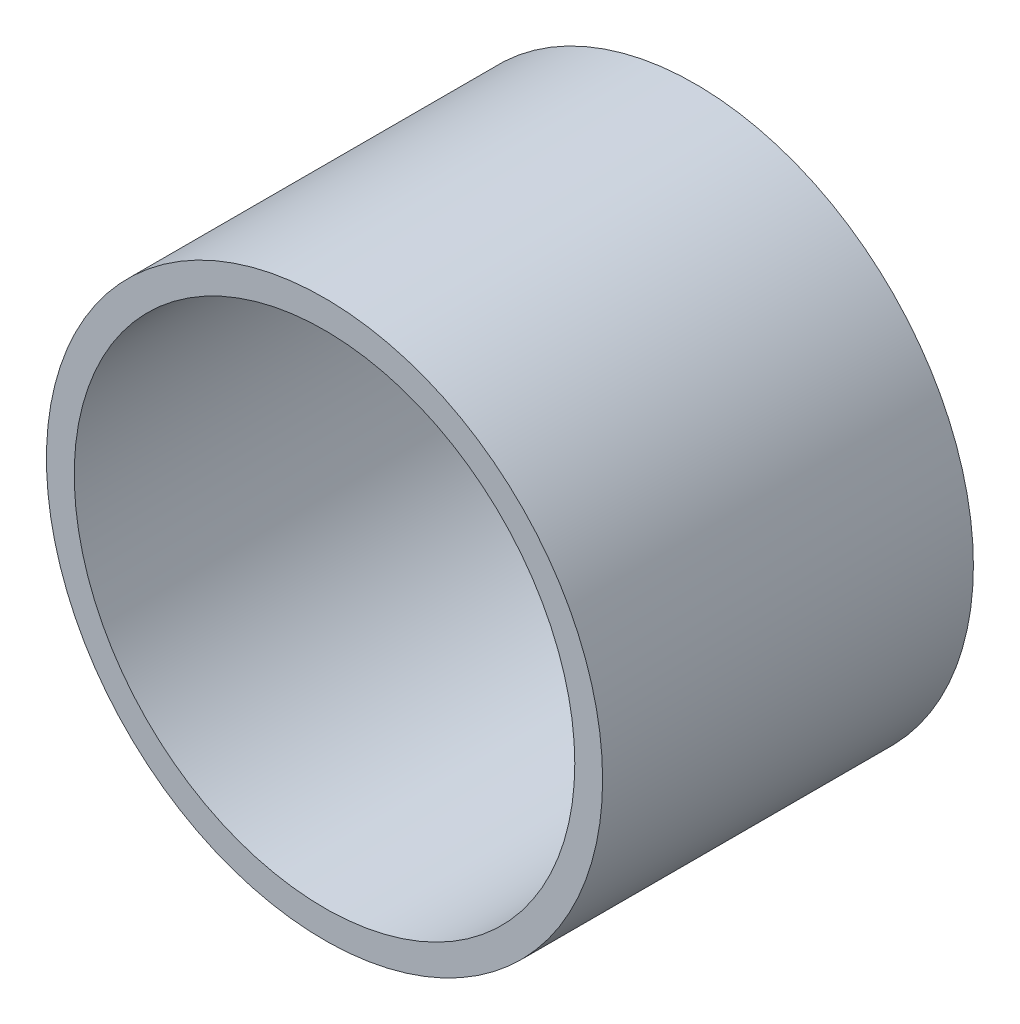
SolidWorks part; units mm, degrees
ref_plane "Front Plane" through (0, 0, 0) normal (0, 0, 1) x (1, 0, 0)
ref_plane "Top Plane" through (0, 0, 0) normal (0, 1, 0) x (1, 0, 0)
ref_plane "Right Plane" through (0, 0, 0) normal (1, 0, 0) x (0, 0, -1)
sketch "Sketch1" plane through (0, 0, 0) normal (0, 0, 1) x (1, 0, 0)
  circle A0 centre (0, 0) radius 34.29
  circle A1 centre (0, 0) radius 38.1
  dimension "D1" = 76.2
  dimension "D2" = 3.81
extrude "Boss-Extrude1" add sketch "Sketch1" along normal blind 50.8
